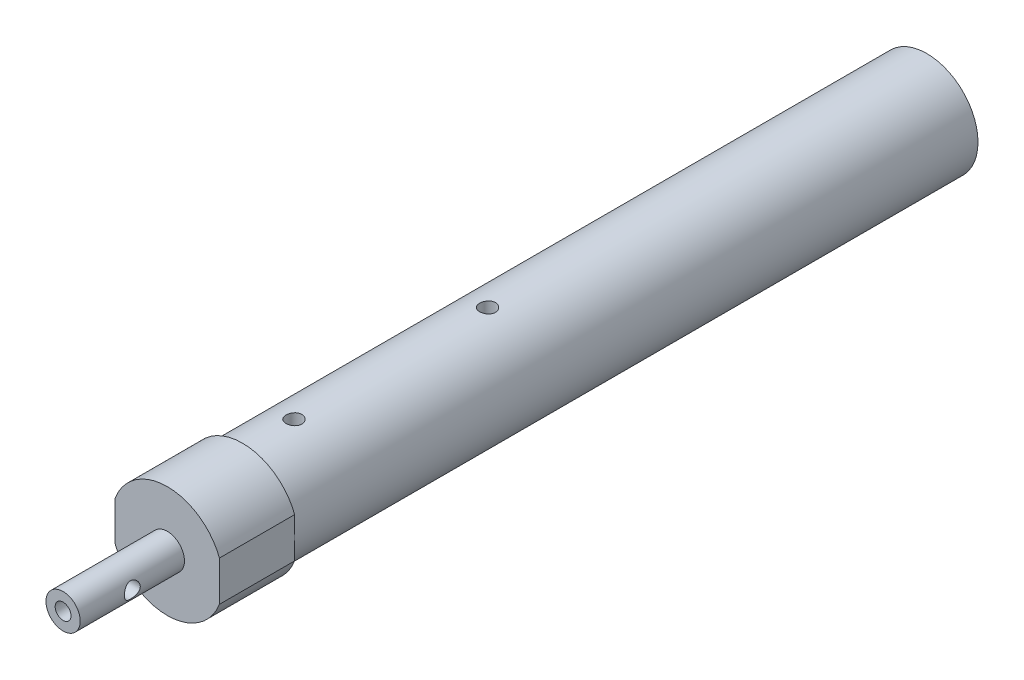
SolidWorks part; units mm, degrees
ref_plane "Front Plane" through (0, 0, 0) normal (0, 0, 1) x (1, 0, 0)
ref_plane "Top Plane" through (0, 0, 0) normal (0, 1, 0) x (1, 0, 0)
ref_plane "Right Plane" through (0, 0, 0) normal (1, 0, 0) x (0, 0, -1)
sketch "Sketch1" plane through (0, 0, 0) normal (0, 0, 1) x (1, 0, 0)
  circle A0 centre (0, 0) radius 8.7312
  dimension "D1" = 17.4625
extrude "Boss-Extrude1" add sketch "Sketch1" along normal blind 129.54
sketch "Sketch2" plane through (0, 0, 129.54) normal (0, 0, 1) x (1, 0, 0)
  circle A0 centre (0, 0) radius 2.921
  dimension "D1" = 5.842
extrude "Boss-Extrude2" add sketch "Sketch2" along normal blind 17.78
ref_plane "Plane1" through (0, 8.7312, 0) normal (0, 1, 0) x (1, 0, 0)
sketch "Sketch4" plane through (0, 8.7312, 0) normal (0, 1, 0) x (1, 0, 0)
  line L1 (-2.921, -147.32) -> (2.921, -147.32) construction
  circle A0 centre (0, -74.93) radius 1.8415
  circle A1 centre (0, -107.95) radius 1.8415
  dimension "D1" = 3.683
  dimension "D2" = 33.02
  dimension "D3" = 39.37
hole_wizard "#6-32 Tapped Hole1" positions "Sketch5" profile "Sketch6" tap size "#6-32" standard "ANSI Inch" end condition through all
sketch "Sketch5" plane through (0, 8.7312, 0) normal (0, 1, 0) x (1, 0, 0)
  point P0 (0, -74.93)
  point P3 (0, -107.95)
sketch "Sketch6" plane through (0, 8.7312, 74.93) normal (1, 0, 0) x (0, 0, 1)
  line L0 (0, 0) -> (0, 17.4625)
  line L1 (0, 17.4625) -> (1.3525, 17.4625)
  line L2 (1.3525, 17.4625) -> (1.3525, 0)
  line L5 (1.3525, 0) -> (0, 0)
  line L11 (0, -6.35) -> (0, 107.95) construction
  dimension "Thru Tap Drill Dia." = 2.7051
  dimension "Thru Tap Drill Depth" = 17.4625
cosmetic thread "Hole Thread1" parameters "D2"=3.5052
cosmetic thread "Hole Thread2" parameters "D2"=3.5052
ref_plane "Plane2" through (2.921, 0, 0) normal (1, 0, 0) x (0, 0, -1)
sketch "Sketch7" plane through (2.921, 0, 0) normal (1, 0, 0) x (0, 0, -1)
  line L1 (-147.32, 2.921) -> (-147.32, -2.921) construction
  circle A0 centre (-138.43, 0) radius 1.8415
  dimension "D1" = 3.683
  dimension "D2" = 8.89
hole_wizard "#6-32 Tapped Hole2" positions "Sketch8" profile "Sketch9" tap size "#6-32" standard "ANSI Inch" end condition through all
sketch "Sketch8" plane through (2.921, 0, 0) normal (1, 0, 0) x (0, 0, -1)
  point P0 (-138.43, 0)
sketch "Sketch9" plane through (2.921, 0, 138.43) normal (0, 1, 0) x (0, 0, -1)
  line L0 (0, 0) -> (0, 11.6522)
  line L1 (0, 11.6522) -> (1.3525, 11.6522)
  line L2 (1.3525, 11.6522) -> (1.3525, 0)
  line L5 (1.3525, 0) -> (0, 0)
  line L11 (0, -6.35) -> (0, 107.95) construction
  dimension "Thru Tap Drill Dia." = 2.7051
  dimension "Thru Tap Drill Depth" = 11.6522
cosmetic thread "Hole Thread3" parameters "D2"=3.5052
sketch "Sketch10" plane through (0, 0, 129.54) normal (0, 0, 1) x (1, 0, 0)
  line L0 (8.89, -3.4196) -> (8.89, 3.4196)
  line L1 (-8.89, -3.4196) -> (-8.89, 3.4196)
  arc A0 (-8.89, -3.4196) -> (8.89, -3.4196) centre (0, 0) ccw
  arc A1 (-8.89, 3.4196) -> (-8.89, -3.4196) centre (0, 0) ccw construction
  arc A2 (8.89, -3.4196) -> (8.89, 3.4196) centre (0, 0) ccw construction
  arc A3 (8.89, 3.4196) -> (-8.89, 3.4196) centre (0, 0) ccw
  dimension "D1" = 19.05
  dimension "D2" = 8.89
  dimension "D3" = 8.89
extrude "Boss-Extrude3" add sketch "Sketch10" against normal blind 12.827
sketch "Sketch11" plane through (0, 0, 147.32) normal (0, 0, 1) x (1, 0, 0)
  point P0 (0, 0)
hole_wizard "#6-32 Tapped Hole3" positions "Sketch12" profile "Sketch13" tap size "#6-32" standard "ANSI Inch"
sketch "Sketch12" plane through (0, 0, 147.32) normal (0, 0, 1) x (1, 0, 0)
  point P0 (0, 0)
sketch "Sketch13" plane through (0, 0, 147.32) normal (1, 0, 0) x (0, -1, 0)
  line L0 (0, 0) -> (0, 5.8927)
  line L1 (0, 5.8927) -> (1.3525, 5.08)
  line L2 (1.3525, 5.08) -> (1.3525, 0)
  line L5 (1.3525, 0) -> (0, 0)
  line L10 (0, 5.8927) -> (-1.3526, 5.08) construction
  line L11 (0, -6.35) -> (0, 107.95) construction
  dimension "Tap Drill Dia." = 2.7051
  dimension "Tap Drill Depth" = 5.08
  dimension "Drill Angle" = 118
